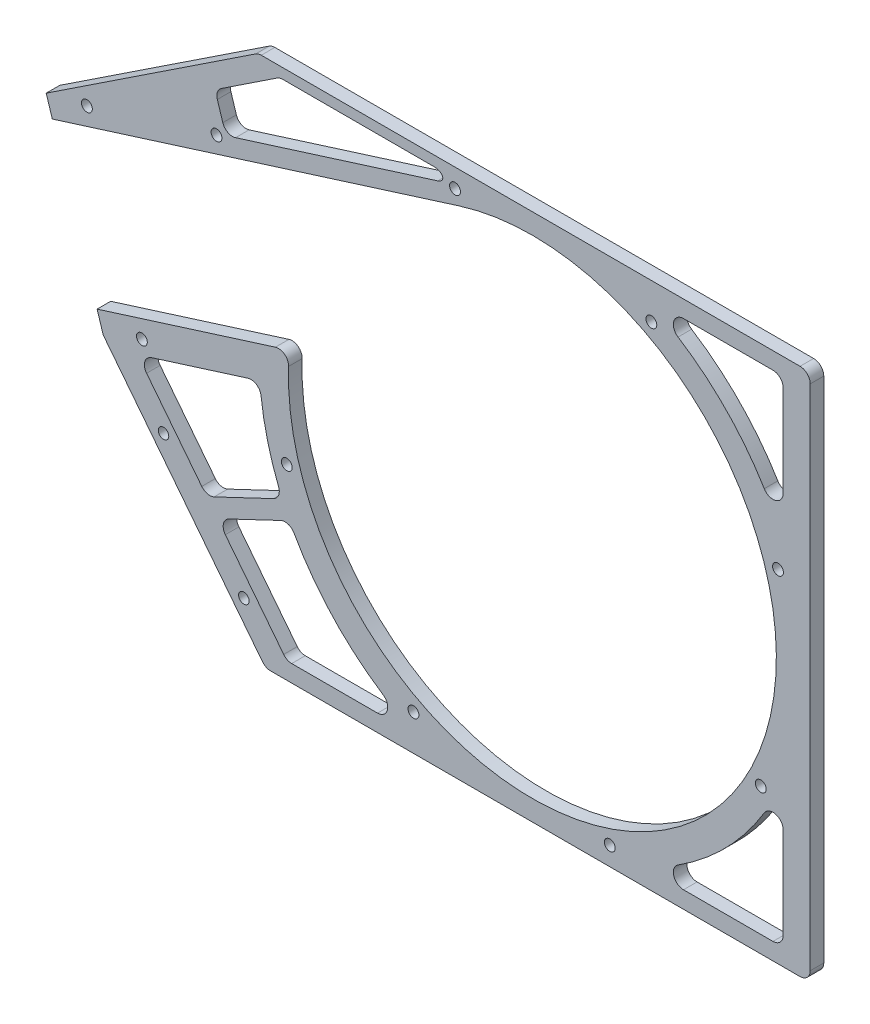
SolidWorks part; units mm, degrees
material "Thornel Mat VMA"
ref_plane "前视基准面" through (0, 0, 0) normal (0, 0, 1) x (1, 0, 0)
ref_plane "上视基准面" through (0, 0, 0) normal (0, 1, 0) x (1, 0, 0)
ref_plane "右视基准面" through (0, 0, 0) normal (1, 0, 0) x (0, 0, -1)
sketch "草图1" plane through (0, 0, 0) normal (0, 0, 1) x (1, 0, 0)
  line L0 (-15.024, 47.6894) -> (0, 0) construction
  line L1 (-15.024, 47.6894) -> (-62.0591, 32.8715) construction
  line L2 (-166.4, 0) -> (-62.0591, 32.8715) construction
  line L3 (-166.4, 0) -> (0, 0) construction
  line L4 (-21.6346, 68.6727) -> (-172.8123, 21.0458) construction
  line L5 (-116.4, -150) -> (-76.4, -150) construction
  line L6 (-116.4, -150) -> (-116.4, 150) construction
  line L7 (-116.4, 150) -> (-76.4, 150) construction
  line L8 (-76.4, -150) -> (-76.4, 150) construction
  line L9 (-96.4, 150) -> (-96.4, -150) construction
  line L10 (-116.4, 0) -> (-76.4, 0) construction
  line L11 (-116.4, -81) -> (116.4, -81)
  line L12 (-116.4, -81) -> (-116.4, 81)
  line L13 (-116.4, 81) -> (116.4, 81)
  line L14 (116.4, -81) -> (116.4, 81)
  line L15 (0, 81) -> (0, -81) construction
  line L16 (-116.4, 0) -> (116.4, 0) construction
  circle A0 centre (0, 0) radius 23 construction
  circle A1 centre (0, 0) radius 50 construction
  circle A2 centre (-36.5877, 34.0784) radius 4.5 construction
  circle A3 centre (-15.024, 47.6894) radius 21 construction
  circle A4 centre (-62.0591, 32.8715) radius 21 construction
  circle A5 centre (0, 0) radius 72
  circle A6 centre (-166.4, 0) radius 60 construction
  point P14 (-96.4, 0)
  dimension "D1" = 46
  dimension "D2" = 100
  dimension "D3" = 9
  dimension "D4" = 42
  dimension "D5" = 144
  dimension "D6" = 120
  dimension "D7" = 40
  dimension "D8" = 50
  dimension "D9" = 166.4
  dimension "D10" = 300
  dimension "D11" = 4.4
  dimension "D12" = 162
  dimension "D13" = 50
extrude "凸台-拉伸1" add sketch "草图1" along normal blind 4 contours L11 L14 L13 L12 A5 region at (-113.5638, 0, 0)
sketch "草图3" plane through (0, 0, 4) normal (0, 0, 1) x (1, 0, 0)
  line L0 (-21.6346, 68.6727) -> (-172.8123, 21.0458) construction
  line L1 (-21.6346, 68.6727) -> (-116.4, 38.8179)
  line L7 (-71.6806, 6.7744) -> (-116.4, -7.314)
  line L8 (-21.6346, 68.6727) -> (-172.4293, 21.1665) construction
  line L9 (-116.4, -81) -> (-116.4, 81) construction
  line L10 (-8.4135, 26.7061) -> (-159.2081, -20.8002) construction
  line L11 (-116.4, 38.8179) -> (-116.4, -7.314)
  circle A0 centre (0, 0) radius 72 construction
  arc A1 (-21.6346, 68.6727) -> (-71.6806, 6.7744) centre (0, 0) ccw
  dimension "D1" = 44
extrude "切除-拉伸2" cut sketch "草图3" against normal blind 10
sketch "草图6" plane through (0, 0, 4) normal (0, 0, 1) x (1, 0, 0)
  line L1 (-131.789, 9.054) -> (-132.9201, 12.6444) construction
  line L2 (-76.4, -81) -> (-126.6717, -16.8406)
  line L3 (-116.4, -81) -> (116.4, -81) construction
  line L4 (-76.4, -150) -> (-76.4, 150) construction
  line L5 (-126.6717, -16.8406) -> (-128.4745, -11.1179)
  line L6 (-143.4986, 36.5715) -> (-76.4, 81)
  line L7 (-116.4, 81) -> (116.4, 81) construction
  line L8 (-166.4, 0) -> (-62.0591, 32.8715) construction
  line L9 (-76.4, 81) -> (-76.4, 51.4195)
  line L10 (-141.6957, 30.8488) -> (-76.4, 51.4195)
  line L11 (-21.6346, 68.6727) -> (-172.8123, 21.0458) construction
  line L12 (-71.6806, 6.7744) -> (-128.4745, -11.1179)
  line L13 (-116.4, -7.314) -> (-71.6806, 6.7744) construction
  line L14 (-141.6957, 30.8488) -> (-143.4986, 36.5715)
  line L15 (-76.4, 5.2876) -> (-76.4, -81)
  line M2 (-116.4, -7.314) -> (-116.4, -81)
  line M3 (-116.4, -81) -> (116.4, -81)
  line M4 (116.4, -81) -> (116.4, 81)
  line M5 (116.4, 81) -> (-116.4, 81)
  line M6 (-116.4, 81) -> (-116.4, 38.8179)
  line M7 (-116.4, 38.8179) -> (-21.6346, 68.6727)
  arc M8 (-21.6346, 68.6727) -> (-71.6806, 6.7744) centre (0, 0) cw
  dimension "D1" = 2.9
  dimension "D2" = 28
  dimension "D3" = 28
  dimension "D4" = 122.9782
  dimension "D5" = 133.5202
  dimension "D6" = 131.789
  dimension "D7" = 131.789
  dimension "D8" = 90
extrude "凸台-拉伸2" add sketch "草图6" against normal up to surface (4 mm away) contours L12 L5 L2 M2 | L15 L12 L2 M2 | L9 L6 M6 M7 | L14 L10 L6 M6 | L15 L9 M8 M3 M4 M5 M7 region at (-92.5042, -30.1164, 4) region at (-73.8817, -37.8562, 4) region at (-120.815, -16.4891, 4) region at (-94.3557, 57.4368, 4) region at (-127.7285, 41.1536, 4) up to face at (-27.9336, 2.9949, 0)
sketch "草图7" plane through (0, 0, 4) normal (0, 0, 1) x (1, 0, 0)
  line L0 (-116.4, -29.9499) -> (-76.4, -81)
  line L1 (-116.4, -81) -> (116.4, -81) construction
  line L2 (-76.4, -81) -> (-116.4, -81)
  line L3 (-116.4, -81) -> (-116.4, -29.9499)
  line L5 (-116.4, -29.9499) -> (-126.6717, -16.8406) construction
  line L6 (-116.4, 54.5145) -> (-76.4, 81)
  line L7 (-116.4, 81) -> (116.4, 81) construction
  line L8 (-76.4, -150) -> (-76.4, 150) construction
  line L9 (-76.4, 81) -> (-116.4, 81)
  line L10 (-116.4, 81) -> (-116.4, 54.5145)
extrude "切除-拉伸3" cut sketch "草图7" against normal blind 10
sketch "草图5" plane through (0, 0, 4) normal (0, 0, 1) x (1, 0, 0)
  line L0 (-131.485, 39.3078) -> (0, 39.3078) construction
  line L1 (0, 39.3078) -> (0, 0) construction
  line L2 (0, 0) -> (0, -12.1968) construction
  line L3 (0, -12.1968) -> (-115.2591, -12.1968) construction
  arc A0 (-128.111, 41.4562) -> (-135.3002, 38.1058) centre (-131.485, 39.3078) ccw construction
  arc A1 (-119.0742, -13.3987) -> (-111.2628, -12.0232) centre (-115.2591, -12.1968) ccw construction
  circle A2 centre (-115.2591, -12.1968) radius 1.6
  circle A3 centre (-131.485, 39.3078) radius 1.6
  dimension "D5" = 3.2
extrude "切除-拉伸4" cut sketch "草图5" against normal blind 10
sketch "草图9" plane through (0, 0, 4) normal (0, 0, 1) x (1, 0, 0)
  line L1 (72.4879, -0.6203) -> (72.4879, 22.8365) construction
  line L2 (-22.8365, 72.4879) -> (0.6203, 72.4879) construction
  circle A0 centre (-22.8365, 72.4879) radius 1.6 construction
  circle A1 centre (72.4879, 22.8365) radius 1.6 construction
  circle A2 centre (22.8365, -72.4879) radius 1.6 construction
  circle A3 centre (-72.4879, -22.8365) radius 1.6 construction
  circle A4 centre (-22.8365, 72.4879) radius 1.6
  circle A5 centre (72.4879, 22.8365) radius 1.6
  circle A6 centre (22.8365, -72.4879) radius 1.6
  circle A7 centre (-72.4879, -22.8365) radius 1.6
  dimension "D9" = 3.2
  dimension "D5" = 23.4568
  dimension "D6" = 23.4568
extrude "切除-拉伸5" cut sketch "草图9" against normal blind 10
sketch "草图10" plane through (0, 0, 4) normal (0, 0, 1) x (1, 0, 0)
  line L0 (-131.485, 39.3078) -> (-93.2292, 50.9907) construction
  line L1 (-93.2292, 50.9907) -> (-22.8365, 72.4879) construction
  circle A0 centre (-93.2292, 50.9907) radius 1.6
  dimension "D1" = 3.2
  dimension "D2" = 40
extrude "切除-拉伸6" cut sketch "草图10" against normal blind 10
sketch "草图11" plane through (0, 0, 0) normal (0, 0, -1) x (-1, 0, 0)
  circle A0 centre (-35.1088, 67.4045) radius 1.6 construction
  circle A1 centre (-67.4045, -35.1088) radius 1.6 construction
  circle A2 centre (35.1088, -67.4045) radius 1.6 construction
  circle A3 centre (-35.1088, 67.4045) radius 1.6
  circle A4 centre (-67.4045, -35.1088) radius 1.6
  circle A5 centre (35.1088, -67.4045) radius 1.6
  dimension "D7" = 3.2
extrude "切除-拉伸7" cut sketch "草图11" against normal blind 10
sketch "草图12" plane through (0, 0, 4) normal (0, 0, 1) x (1, 0, 0)
  line L0 (-93.6687, 62.3697) -> (-74.5936, 75)
  line L1 (-74.5936, 75) -> (-25.8365, 75)
  line L2 (-25.8365, 75) -> (-25.8365, 72.5912)
  line L3 (-25.8365, 72.5912) -> (-90.4736, 52.228)
  line L4 (-90.4736, 52.228) -> (-93.6687, 62.3697)
  line L5 (-21.6346, 68.6727) -> (-141.6957, 30.8488) construction
  line L6 (-143.4986, 36.5715) -> (-76.4, 81) construction
  line L7 (-76.4, 81) -> (116.4, 81) construction
  circle A0 centre (-93.2292, 50.9907) radius 1.6 construction
  circle A1 centre (-22.8365, 72.4879) radius 1.6 construction
  dimension "D2" = 3
  dimension "D1" = 5
  dimension "D3" = 6
  dimension "D4" = 6
  dimension "D5" = 3
extrude "切除-拉伸8" cut sketch "草图12" against normal blind 10
fillet "圆角1" radius 3 5 edges at (-25.8365, 75, 2) (-25.8365, 72.5912, 2) (-90.4736, 52.228, 2) (-93.6687, 62.3697, 2) (-74.5936, 75, 2)
fillet "圆角2" radius 1.1 1 edges at (-26.181, 73.3957, 2)
fillet "圆角3" radius 3 3 edges at (-71.6806, 6.7744, 2) (-76.4, -81, 2) (-76.4, 81, 2)
sketch "草图13" plane through (0, 0, 4) normal (0, 0, 1) x (1, 0, 0)
  line L0 (-116.5439, -16.7953) -> (-80.4179, -5.4143)
  line L1 (-116.5439, -16.7953) -> (-72.5051, -73)
  line L2 (-72.5051, -73) -> (-34.1667, -73)
  line L3 (-77.3008, -79.8503) -> (-126.6717, -16.8406) construction
  line L4 (-128.4745, -11.1179) -> (-75.8564, 5.4589) construction
  line L5 (-74.9394, -81) -> (116.4, -81) construction
  line L6 (-94.5245, -44.8977) -> (-72.8046, -34.5811) construction
  line L7 (-92.9441, -46.9147) -> (-71.697, -36.8226)
  line L8 (-96.1049, -42.8807) -> (-73.8422, -32.3062)
  line L9 (-95.5971, -42.6395) -> (-73.8772, -32.3229) construction
  line L10 (-93.4519, -47.1559) -> (-71.732, -36.8393) construction
  arc A0 (-80.4179, -5.4143) -> (-34.1667, -73) centre (0, 0) ccw
  circle A1 centre (-72.4879, -22.8365) radius 1.6 construction
  dimension "D1" = 3
  dimension "D2" = 8
  dimension "D3" = 9
  dimension "D4" = 8
  dimension "D5" = 2.5
  dimension "D6" = 2.5
extrude "切除-拉伸9" cut sketch "草图13" against normal blind 10 contours A0 L7 L1 L2 | A0 L0 L1 L8 region at (-92.8961, -23.6843, 4) region at (-68.4056, -58.1405, 4)
fillet "圆角4" radius 3 8 edges at (-73.8422, -32.3062, 2) (-96.1049, -42.8807, 2) (-34.1667, -73, 2) (-72.5051, -73, 2) (-92.9441, -46.9147, 2) (-71.697, -36.8226, 2) (-116.5439, -16.7953, 2) (-80.4179, -5.4143, 2)
sketch "草图14" plane through (0, 0, 4) normal (0, 0, 1) x (1, 0, 0)
  line L0 (82, 81) -> (82, -81)
  line L1 (-75.4968, 81) -> (116.4, 81) construction
  line L2 (-74.9394, -81) -> (116.4, -81) construction
  line L3 (82, 81) -> (116.4, 81)
  line L4 (116.4, 81) -> (116.4, -81)
  line L5 (116.4, -81) -> (82, -81)
  arc A1 (-71.9568, 2.4936) -> (-21.6346, 68.6727) centre (0, 0) ccw construction
  dimension "D1" = 10
extrude "切除-拉伸10" cut sketch "草图14" against normal blind 10
sketch "草图15" plane through (0, 0, 4) normal (0, 0, 1) x (1, 0, 0)
  line L0 (32.7261, 73) -> (74, 73)
  line L1 (74, 73) -> (74, 30.3974)
  line L2 (-75.4968, 81) -> (82, 81) construction
  line L3 (82, 81) -> (82, -81) construction
  line L4 (0, 0) -> (119.3525, 0) construction
  line L5 (74, -73) -> (74, -30.3974)
  line L6 (32.7261, -73) -> (74, -73)
  arc A0 (74, 30.3974) -> (32.7261, 73) centre (0, 0) ccw
  arc A1 (-71.9568, 2.4936) -> (-21.6346, 68.6727) centre (0, 0) ccw construction
  arc A2 (74, -30.3974) -> (32.7261, -73) centre (0, 0) cw
  dimension "D1" = 8
  dimension "D2" = 8
  dimension "D3" = 8
extrude "切除-拉伸11" cut sketch "草图15" against normal blind 10
fillet "圆角5" radius 3 8 edges at (74, 30.3974, 2) (32.7261, 73, 2) (74, 73, 2) (82, 81, 2) (32.7261, -73, 2) (74, -30.3974, 2) (74, -73, 2) (82, -81, 2)
sketch "草图16" plane through (0, 0, 0) normal (0, 0, -1) x (-1, 0, 0)
  line L0 (105.7287, -30.5983) -> (112.0259, -35.5324) construction
  line L1 (113.872, -20.2053) -> (97.5853, -40.9913) construction
  line L2 (126.6717, -16.8406) -> (77.3008, -79.8503) construction
  line L3 (82.0187, -60.8582) -> (88.3159, -65.7923) construction
  line L4 (90.6315, -49.8661) -> (73.4059, -71.8503) construction
  line L5 (85.1673, -63.3253) -> (108.8773, -33.0653) construction
  circle A0 centre (108.8773, -33.0653) radius 1.55
  circle A1 centre (85.1673, -63.3253) radius 1.55
  dimension "D1" = 3.1
extrude "切除-拉伸12" cut sketch "草图16" against normal blind 10
sketch "草图17" plane through (0, 0, 4) normal (0, 0, 1) x (1, 0, 0)
  line L0 (100, -78) -> (100, 78) construction
  line L1 (-100, 88) -> (100, 88)
  line L2 (-100, 88) -> (-100, 78)
  line L3 (-100, 78) -> (100, 78)
  line L4 (100, 88) -> (100, 78)
  line L5 (-100, -78) -> (100, -78)
  line L6 (-100, -78) -> (-100, -88)
  line L7 (-100, -88) -> (100, -88)
  line L8 (100, -78) -> (100, -88)
  point P8 (100, 0)
  point P9 (0, -78)
  dimension "D1" = 156
  dimension "D2" = 10
  dimension "D3" = 200
extrude "切除-拉伸13" cut sketch "草图17" against normal mid plane 10
fillet "圆角6" radius 3 4 edges at (82, 78, 2) (-80.9308, 78, 2) (-78.7506, -78, 2) (82, -78, 2)
